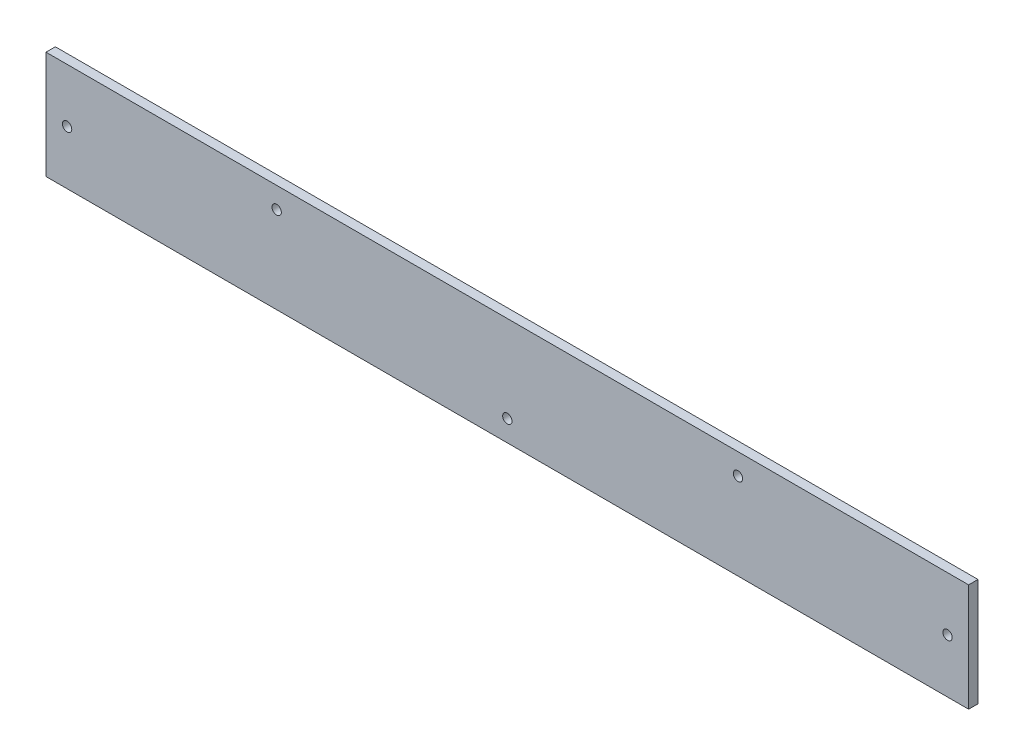
SolidWorks part; units mm, degrees
ref_plane "Piano frontale" through (0, 0, 0) normal (0, 0, 1) x (1, 0, 0)
ref_plane "Piano superiore" through (0, 0, 0) normal (0, 1, 0) x (1, 0, 0)
ref_plane "Piano destro" through (0, 0, 0) normal (1, 0, 0) x (0, 0, -1)
sketch "Schizzo1" plane through (0, 0, 0) normal (0, 0, 1) x (1, 0, 0)
  line L0 (0, 0) -> (0, 46)
  line L1 (0, 46) -> (394, 46)
  line L2 (394, 46) -> (394, 0)
  line L3 (394, 0) -> (0, 0)
  line L4 (0, 23) -> (394, 23) construction
  line L5 (197, 42) -> (197, 123.488) construction
  line L6 (0, 0) -> (197, 46) construction
  line L7 (98.5, 23) -> (98.5, 46) construction
  circle A0 centre (9, 23) radius 2
  circle A1 centre (98.5, 37) radius 2
  circle A2 centre (197, 9) radius 2
  circle A3 centre (385, 23) radius 2
  circle A4 centre (295.5, 37) radius 2
  dimension "D3" = 9
  dimension "D4" = 9
  dimension "D6" = 4
  dimension "D5" = 4
  dimension "D8" = 4
  dimension "D9" = 4
  dimension "D1" = 46
  dimension "D2" = 394
  dimension "D7" = 9
  dimension "D10" = 9
extrude "Estrusione-Estrusione1" add sketch "Schizzo1" along normal blind 4
